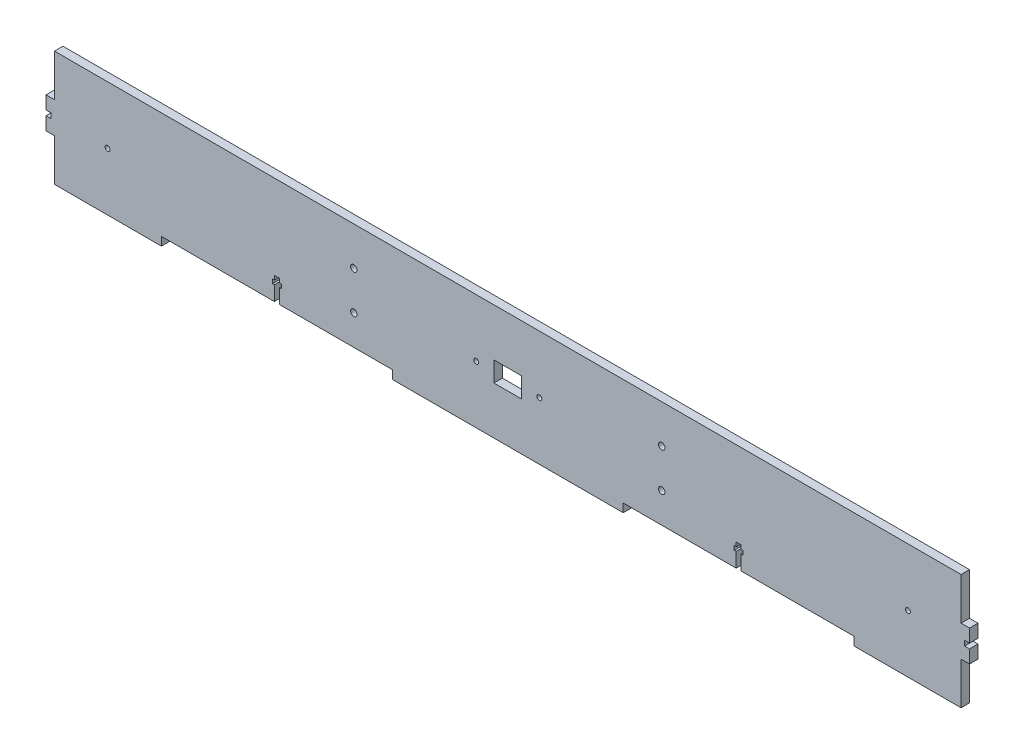
SolidWorks part; units mm, degrees
ref_plane "Front Plane" through (0, 0, 0) normal (0, 0, 1) x (1, 0, 0)
ref_plane "Top Plane" through (0, 0, 0) normal (0, 1, 0) x (1, 0, 0)
ref_plane "Right Plane" through (0, 0, 0) normal (1, 0, 0) x (0, 0, -1)
sketch "Sketch1" plane through (0, 0, 0) normal (0, 0, 1) x (1, 0, 0)
  line L0 (308.5, 78) -> (308.5, 50.625)
  line L1 (308.5, 50.625) -> (303, 50.625)
  line L2 (303, 50.625) -> (303, 42.125)
  line L3 (303, 42.125) -> (306.25, 42.125)
  line L4 (306.25, 42.125) -> (306.25, 40.5)
  line L5 (306.25, 40.5) -> (306.25, 38.875)
  line L6 (306.25, 38.875) -> (303, 38.875)
  line L7 (303, 38.875) -> (303, 30.375)
  line L8 (303, 30.375) -> (308.5, 30.375)
  line L9 (308.5, 30.375) -> (308.5, 3)
  line L10 (308.5, 3) -> (378, 3)
  line L11 (378, 3) -> (378, 8.5)
  line L12 (378, 8.5) -> (451.375, 8.5)
  line L13 (451.375, 8.5) -> (451.375, 17.95)
  line L14 (451.375, 17.95) -> (450.125, 17.95)
  line L15 (450.125, 17.95) -> (450.125, 20.6)
  line L16 (450.125, 20.6) -> (451.375, 20.6)
  line L17 (451.375, 20.6) -> (451.375, 23.25)
  line L18 (451.375, 23.25) -> (454.625, 23.25)
  line L19 (454.625, 23.25) -> (454.625, 20.6)
  line L20 (454.625, 20.6) -> (455.875, 20.6)
  line L21 (455.875, 20.6) -> (455.875, 17.95)
  line L22 (455.875, 17.95) -> (454.625, 17.95)
  line L23 (454.625, 17.95) -> (454.625, 8.5)
  line L24 (454.625, 8.5) -> (528, 8.5)
  line L25 (528, 8.5) -> (528, 3)
  line L26 (528, 3) -> (678, 3)
  line L27 (678, 3) -> (678, 8.5)
  line L28 (678, 8.5) -> (751.375, 8.5)
  line L29 (751.375, 8.5) -> (751.375, 17.95)
  line L30 (751.375, 17.95) -> (750.125, 17.95)
  line L31 (750.125, 17.95) -> (750.125, 20.6)
  line L32 (750.125, 20.6) -> (751.375, 20.6)
  line L33 (751.375, 20.6) -> (751.375, 23.25)
  line L34 (751.375, 23.25) -> (754.625, 23.25)
  line L35 (754.625, 23.25) -> (754.625, 20.6)
  line L36 (754.625, 20.6) -> (755.875, 20.6)
  line L37 (755.875, 20.6) -> (755.875, 17.95)
  line L38 (755.875, 17.95) -> (754.625, 17.95)
  line L39 (754.625, 17.95) -> (754.625, 8.5)
  line L40 (754.625, 8.5) -> (828, 8.5)
  line L41 (828, 8.5) -> (828, 3)
  line L42 (828, 3) -> (897.5, 3)
  line L43 (897.5, 3) -> (897.5, 30.375)
  line L44 (897.5, 30.375) -> (903, 30.375)
  line L45 (903, 30.375) -> (903, 38.875)
  line L46 (903, 38.875) -> (899.75, 38.875)
  line L47 (899.75, 38.875) -> (899.75, 40.5)
  line L48 (899.75, 40.5) -> (899.75, 42.125)
  line L49 (899.75, 42.125) -> (903, 42.125)
  line L50 (903, 42.125) -> (903, 50.625)
  line L51 (903, 50.625) -> (897.5, 50.625)
  line L52 (897.5, 50.625) -> (897.5, 78)
  line L53 (897.5, 78) -> (308.5, 78)
extrude "Boss-Extrude1" add sketch "Sketch1" along normal blind 5.5
sketch "Sketch2" plane through (0, 0, 5.5) normal (0, 0, 1) x (1, 0, 0)
  line L0 (582.5, 40.5) -> (623.5, 40.5)
  line L1 (897.5, 78) -> (308.5, 78) construction
  line L2 (306.25, 42.125) -> (306.25, 38.875) construction
  line L4 (594, 47) -> (612, 47)
  line L5 (594, 47) -> (594, 34)
  line L6 (594, 34) -> (612, 34)
  line L7 (612, 47) -> (612, 34)
  circle A0 centre (582.5, 40.5) radius 1.6
  circle A1 centre (623.5, 40.5) radius 1.6
  point P4 (603, 40.5)
  point P7 (603, 78)
  point P8 (612, 40.5)
  point P11 (306.25, 40.5)
  point P16 (603, 47)
  dimension "D1" = 3.2
  dimension "D2" = 41
  dimension "D3" = 13
  dimension "D4" = 18
extrude "Cut-Extrude1" cut sketch "Sketch2" against normal through all both and the other way through all contours A1 | A0 | L7 L0 L5 L6 | L7 L4 L5 L0 region at (623.5, 42.0547, 5.5) region at (603, 43.75, 5.5) region at (603, 37.25, 5.5) region at (580.9453, 40.5, 5.5)
sketch "Sketch3" plane through (0, 0, 5.5) normal (0, 0, 1) x (1, 0, 0)
  line L1 (503, 53) -> (703, 53)
  line L2 (503, 53) -> (503, 28)
  line L3 (503, 28) -> (703, 28)
  line L4 (703, 53) -> (703, 28)
  line L5 (897.5, 78) -> (308.5, 78) construction
  circle A0 centre (503, 53) radius 2.1
  circle A1 centre (503, 28) radius 2.1
  circle A2 centre (703, 28) radius 2.1
  circle A3 centre (703, 53) radius 2.1
  point P4 (603, 53)
  point P7 (603, 78)
  dimension "D4" = 4.2
  dimension "D1" = 25
  dimension "D2" = 200
  dimension "D3" = 25
extrude "Cut-Extrude2" cut sketch "Sketch3" against normal through all contours A0 | A1 | A2 | A3
sketch "Sketch4" plane through (0, 0, 5.5) normal (0, 0, 1) x (1, 0, 0)
  line L0 (306.25, 42.125) -> (306.25, 38.875) construction
  line L1 (303, 50.625) -> (303, 42.125) construction
  line L2 (903, 42.125) -> (903, 50.625) construction
  circle A0 centre (343, 40.5) radius 1.6
  circle A1 centre (863, 40.5) radius 1.6
  point P4 (0, 0)
  point P7 (306.25, 40.5)
  point P10 (0, 0)
  dimension "D3" = 3.2
  dimension "D1" = 40
  dimension "D2" = 40
extrude "Cut-Extrude3" cut sketch "Sketch4" against normal through all
